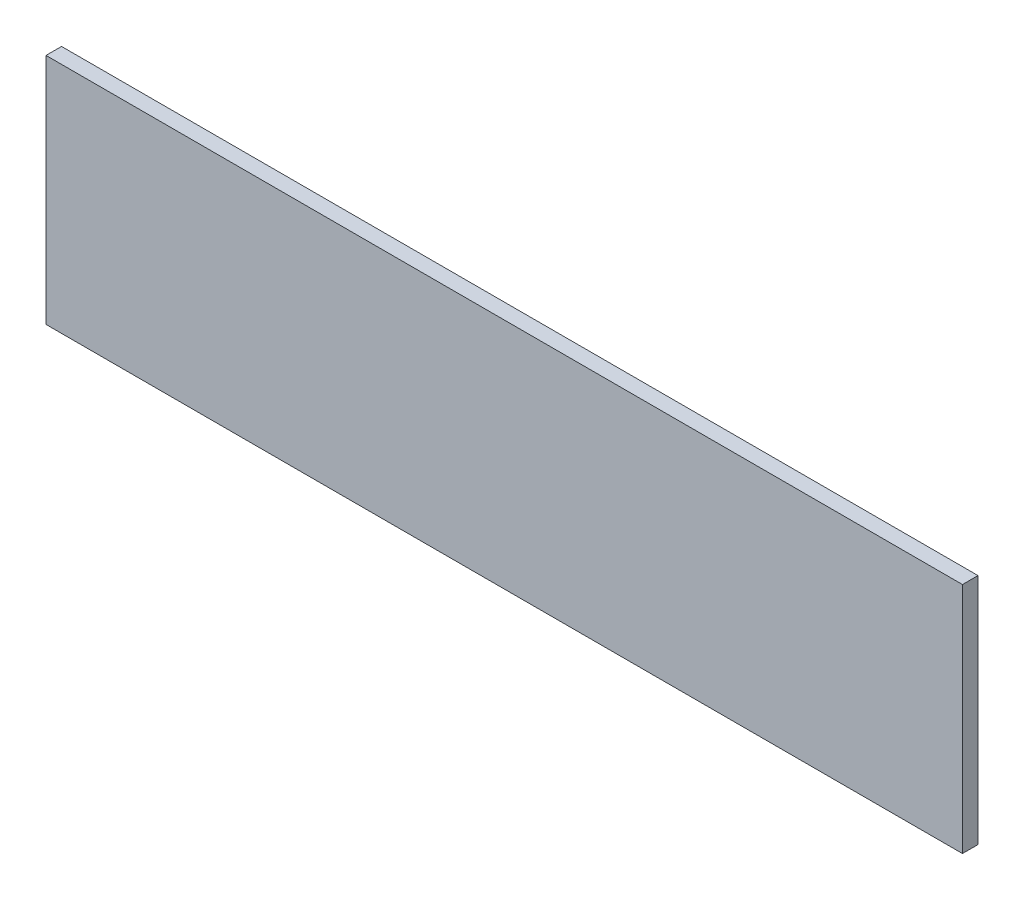
SolidWorks part; units mm, degrees
ref_plane "Ebene vorne" through (0, 0, 0) normal (0, 0, 1) x (1, 0, 0)
ref_plane "Ebene oben" through (0, 0, 0) normal (0, 1, 0) x (1, 0, 0)
ref_plane "Ebene rechts" through (0, 0, 0) normal (1, 0, 0) x (0, 0, -1)
sketch "Skizze1" plane through (0, 0, 0) normal (0, 0, 1) x (1, 0, 0)
  line L1 (295, 75) -> (-295, 75)
  line L2 (295, 75) -> (295, -75)
  line L3 (295, -75) -> (-295, -75)
  line L4 (-295, 75) -> (-295, -75)
  line L5 (295, 75) -> (-295, -75) construction
  line L6 (295, -75) -> (-295, 75) construction
  point P0 (0, 0)
  dimension "D1" = 150
  dimension "D2" = 590
extrude "Aufsatz-Linear austragen1" add sketch "Skizze1" along normal blind 10
